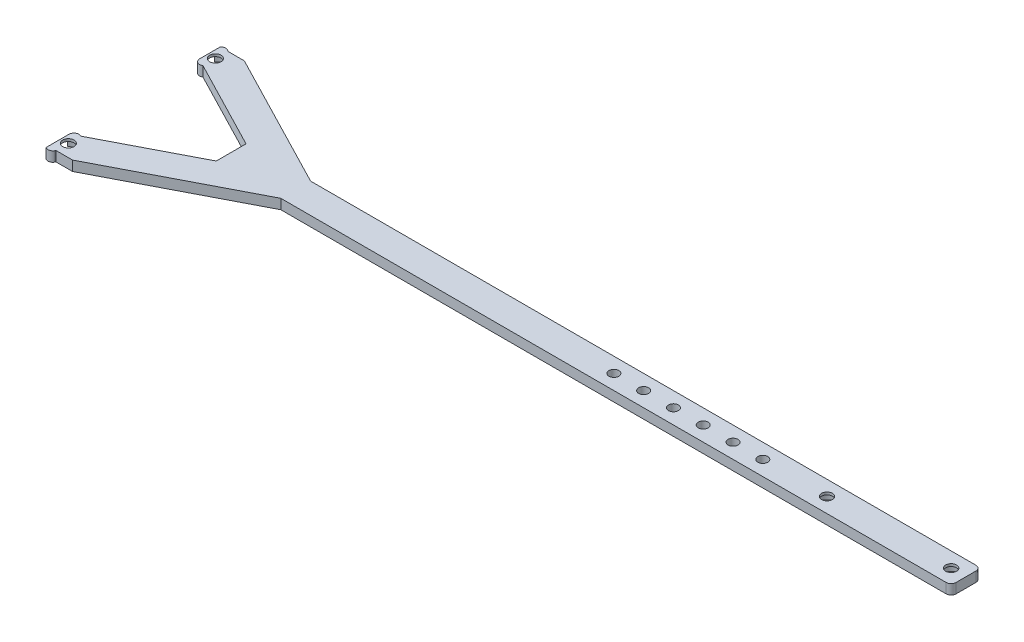
SolidWorks part; units mm, degrees
ref_plane "Płaszczyzna przednia" through (0, 0, 0) normal (0, 0, 1) x (1, 0, 0)
ref_plane "Płaszczyzna górna" through (0, 0, 0) normal (0, 1, 0) x (1, 0, 0)
ref_plane "Płaszczyzna prawa" through (0, 0, 0) normal (1, 0, 0) x (0, 0, -1)
sketch "Szkic1" plane through (0, -0.6011, 0) normal (0, -1, 0) x (1, 0, 0)
  line L0 (-40.95, 47.1335) -> (-28.6, 47.1335) construction
  line L1 (-28.6, 41.1335) -> (-40.95, 41.1335) construction
  line L2 (-159.9499, 47.1335) -> (-28.6, 47.1335)
  line L3 (-28.6, 41.1335) -> (-159.9499, 41.1335)
  line L4 (-28.6, 41.1335) -> (-11.9498, 41.1335)
  line L5 (-11.9498, 41.1335) -> (-11.9498, 47.1335)
  line L6 (-11.9498, 47.1335) -> (-28.6, 47.1335)
  line L7 (-159.9499, 41.1335) -> (-159.9499, 47.1335)
  circle A0 centre (-14.9498, 44.1337) radius 1.1 construction
  circle A1 centre (-39.9499, 44.1337) radius 1.1 construction
  circle A2 centre (-14.9498, 44.1337) radius 1.1
  circle A3 centre (-39.9499, 44.1337) radius 1.1
  dimension "D1" = 3
  dimension "D2" = 120
extrude "Dodanie-wyciągnięcie1" add sketch "Szkic1" along normal blind 2
sketch "Szkic2" plane through (0, -0.6011, 0) normal (0, 1, 0) x (1, 0, 0)
  line L0 (-177.9299, -26.8335) -> (-178.5249, -25.6335) construction
  line L1 (-179.4499, -32.9335) -> (-177.9299, -31.8335) construction
  line L2 (-178.5249, -62.6335) -> (-177.9299, -61.4335) construction
  line L3 (-177.9299, -56.4335) -> (-179.4499, -55.3335) construction
  line L4 (-177.9299, -26.8335) -> (-178.5249, -25.6335)
  line L5 (-179.4499, -32.9335) -> (-177.9299, -31.8335)
  line L6 (-178.5249, -62.6335) -> (-177.9299, -61.4335)
  line L7 (-177.9299, -56.4335) -> (-179.4499, -55.3335)
  line L8 (-178.5249, -25.6335) -> (-179.4499, -26.8335)
  line L9 (-179.4499, -26.8335) -> (-179.4499, -32.9335)
  line L10 (-178.5249, -62.6335) -> (-179.4499, -61.9205)
  line L11 (-179.4499, -61.9205) -> (-179.4499, -55.3335)
  line L12 (-177.9299, -26.8335) -> (-174.5965, -26.8335)
  line L13 (-174.5965, -26.8335) -> (-146.9499, -41.1335)
  line L14 (-159.9499, -41.1335) -> (-159.9499, -47.1335)
  line L15 (-159.9499, -41.1335) -> (-11.9498, -41.1335) construction
  line L16 (-174.5965, -61.4335) -> (-177.9299, -61.4335)
  line L18 (-146.9499, -47.1335) -> (-174.5965, -61.4335)
  line L19 (-11.9498, -47.1335) -> (-159.9499, -47.1335) construction
  line L20 (-177.9299, -56.4335) -> (-159.9499, -47.1335)
  line L21 (-159.9499, -41.1335) -> (-177.9299, -31.8335)
  line L22 (-146.9499, -41.1335) -> (-146.9499, -47.1335)
  circle A0 centre (-177.9297, -58.9335) radius 1.15 construction
  circle A1 centre (-177.9297, -29.3335) radius 1.15 construction
  circle A2 centre (-177.9297, -58.9335) radius 1.15
  circle A3 centre (-177.9297, -29.3335) radius 1.15
  circle A4 centre (-39.9499, -44.1337) radius 1.1 construction
  dimension "D1" = 107
extrude "Dodanie-wyciągnięcie3" add sketch "Szkic2" against normal blind 2
sketch "Szkic4" plane through (0, -2.6011, 0) normal (0, -1, 0) x (1, 0, 0)
  circle A0 centre (-14.9498, 44.1337) radius 2
  circle A1 centre (-39.9499, 44.1337) radius 2
  circle A2 centre (-177.9297, 58.9335) radius 2
  circle A3 centre (-177.9297, 29.3335) radius 2
  dimension "D1" = 4
extrude "Wytnij-wyciągnięcie2" cut sketch "Szkic4" against normal blind 1.5
sketch "Szkic6" plane through (0, -2.6011, 0) normal (0, -1, 0) x (1, 0, 0)
  line L0 (-158.1419, 44.1335) -> (-152.1419, 44.1335)
  line L1 (-146.9499, 41.1335) -> (-11.9498, 41.1335) construction
  arc A0 (-152.1419, 44.1335) -> (-158.1419, 44.1335) centre (-155.1419, 44.1335) ccw
  dimension "D1" = 6
  dimension "D2" = 3
revolve "Obrót11" add sketch "Szkic6" angle 180 about L0
sketch "Szkic7" plane through (0, -0.6011, 0) normal (0, 1, 0) x (1, 0, 0)
  line L0 (-146.9499, -41.1335) -> (-11.9498, -41.1335) construction
  circle A0 centre (-52.8732, -44.1335) radius 1
  circle A1 centre (-58.8732, -44.1335) radius 1
  circle A2 centre (-64.8732, -44.1335) radius 1
  circle A3 centre (-70.8732, -44.1335) radius 1
  circle A4 centre (-76.8732, -44.1335) radius 1
  circle A5 centre (-82.8732, -44.1335) radius 1
  point P12 (0, 0)
  point P13 (-52.8732, -44.1571)
  dimension "D2" = 2
  dimension "D1" = 3
  dimension "D3" = 6
  dimension "D4" = 6
  dimension "D5" = 6
  dimension "D6" = 6
  dimension "D7" = 6
extrude "Wytnij-wyciągnięcie3" cut sketch "Szkic7" against normal blind 3
fillet "Zaokrąglenie1" radius 1 5 edges at (-179.4499, -1.6011, 55.3335) (-178.5249, -1.6011, 62.6335) (-178.5249, -1.6011, 25.6335) (-11.9498, -1.6011, 47.1335) (-11.9498, -1.6011, 41.1335)
fillet "Zaokrąglenie2" radius 1 1 edges at (-179.4499, -1.6011, 32.9335)
